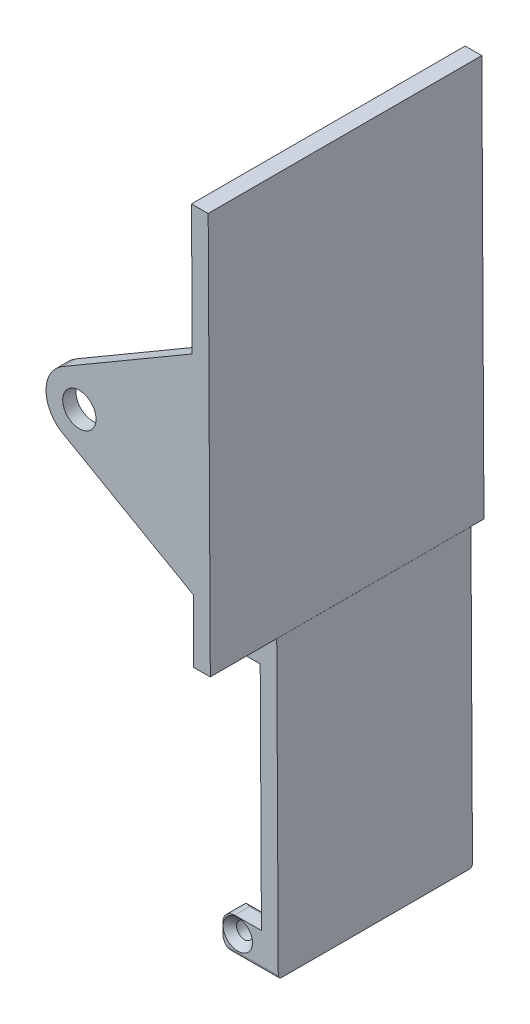
SolidWorks part; units mm, degrees
ref_plane "Front Plane" through (0, 0, 0) normal (0, 0, 1) x (1, 0, 0)
ref_plane "Top Plane" through (0, 0, 0) normal (0, 1, 0) x (1, 0, 0)
ref_plane "Right Plane" through (0, 0, 0) normal (1, 0, 0) x (0, 0, -1)
sketch "Sketch1" plane through (-32.9162, -0.1748, -0.0082) normal (1, 0.0053, 0.0002) x (0.0002, 0, -1)
  line L1 (-31.9268, 49.3585) -> (-29.2268, 49.3585)
  line L2 (-31.9268, 49.3585) -> (-31.9268, 53.8585)
  line L3 (-31.9268, 53.8585) -> (-29.2268, 53.8585)
  line L4 (-29.2268, 49.3585) -> (-29.2268, 53.8585)
  line L5 (-31.9268, 14.8585) -> (-29.2268, 14.8585)
  line L6 (-31.9268, 14.8585) -> (-31.9268, 9.7432)
  line L7 (-31.9268, 9.7432) -> (-29.2268, 9.7432)
  line L8 (-29.2268, 14.8585) -> (-29.2268, 9.7432)
  line L9 (-55.6268, 14.8585) -> (-58.3268, 14.8585)
  line L10 (-55.6268, 14.8585) -> (-55.6268, 9.7432)
  line L11 (-55.6268, 9.7432) -> (-58.3268, 9.7432)
  line L12 (-58.3268, 14.8585) -> (-58.3268, 9.7432)
  line L13 (-55.6268, 49.3585) -> (-58.3268, 49.3585)
  line L14 (-55.6268, 49.3585) -> (-55.6268, 53.8585)
  line L15 (-55.6268, 53.8585) -> (-58.3268, 53.8585)
  line L16 (-58.3268, 49.3585) -> (-58.3268, 53.8585)
  line L18 (-31.9268, 12.8585) -> (-31.9268, 9.0585) construction
  line L19 (-31.9268, 14.8585) -> (-29.2268, 14.8585) construction
  line L20 (-58.3268, 12.8585) -> (-58.3268, 9.0585) construction
  line L21 (-55.6268, 12.8585) -> (-55.6268, 9.0585) construction
  line L22 (-29.2268, 12.8585) -> (-29.2268, 9.0585) construction
  line L23 (-31.9268, 53.8585) -> (-29.2268, 53.8585) construction
  line L24 (-29.2268, 49.3585) -> (-31.9268, 49.3585) construction
  line L25 (-55.6268, 49.3585) -> (-58.3268, 49.3585) construction
  line L26 (-52.7264, 9.723) -> (-36.3268, 9.6085) construction
extrude "Boss-Extrude1" add sketch "Sketch1" along normal blind 5.8 from offset 0.25
sketch "Sketch2" plane through (-26.8663, -0.1427, -0.0067) normal (1, 0.0053, 0.0002) x (0.0002, 0, -1)
  line L1 (-29.2268, 9.7432) -> (-58.3268, 9.7432)
  line L2 (-29.2268, 9.7432) -> (-29.2268, 53.8585)
  line L3 (-29.2268, 53.8585) -> (-58.3268, 53.8585)
  line L4 (-58.3268, 9.7432) -> (-58.3268, 53.8585)
extrude "Boss-Extrude2" add sketch "Sketch2" along normal blind 2.5
hole_wizard "CSK for M2 Countersunk Flat Head Screw1" positions "Sketch4" profile "Sketch5" countersink size "M2" standard "ISO"
sketch "Sketch4" plane through (-0.0145, 0, 58.3268) normal (-0.0002, 0, 1) x (1, 0, 0.0002)
  arc A2 (-30.6956, 52.4462) -> (-30.685, 50.4462) centre (-30.6903, 51.4462) ccw construction
  arc A3 (-30.4885, 13.4467) -> (-30.4779, 11.4468) centre (-30.4832, 12.4468) ccw construction
  point P12 (-30.6903, 51.4462)
  point P14 (-30.4832, 12.4468)
sketch "Sketch5" plane through (-30.7049, 51.4462, 58.3192) normal (0.7071, 0.7071, 0.0002) x (0.7071, -0.7071, 0.0002)
  line L0 (0, 0) -> (0, 4.721)
  line L1 (0, 4.721) -> (1.2, 4)
  line L2 (1.2, 4) -> (1.2, 1)
  line L3 (1.2, 1) -> (2.2, 0)
  line L5 (2.2, 0) -> (0, 0)
  line L6 (-1.2, 1) -> (-2.2, 0) construction
  line L10 (0, 4.721) -> (-1.2, 4) construction
  line L11 (0, -6.35) -> (0, 107.95) construction
  dimension "Hole Dia." = 2.4
  dimension "Hole Depth" = 4
  dimension "Near C'Sink Dia." = 4.4
  dimension "Near C'Sink Angle" = 90
  dimension "Drill Angle" = 118
hole_wizard "CSK for M2 Countersunk Flat Head Screw2" positions "Sketch7" profile "Sketch6" countersink size "M2" standard "ISO"
sketch "Sketch7" plane through (-0.0073, 0, 29.2268) normal (0.0002, 0, -1) x (-1, 0, -0.0002)
  circle A1 centre (30.6903, 51.4462) radius 1.2 construction
  circle A2 centre (30.4832, 12.4468) radius 1.2 construction
  point P0 (30.6903, 51.4462)
  point P5 (30.4832, 12.4468)
sketch "Sketch6" plane through (-30.6976, 51.4462, 29.2192) normal (0.7071, 0.7071, 0.0002) x (-0.7071, 0.7071, -0.0002)
  line L0 (0, 0) -> (0, 4.721)
  line L1 (0, 4.721) -> (1.2, 4)
  line L2 (1.2, 4) -> (1.2, 1)
  line L3 (1.2, 1) -> (2.2, 0)
  line L5 (2.2, 0) -> (0, 0)
  line L6 (-1.2, 1) -> (-2.2, 0) construction
  line L10 (0, 4.721) -> (-1.2, 4) construction
  line L11 (0, -6.35) -> (0, 107.95) construction
  dimension "Hole Dia." = 2.4
  dimension "Hole Depth" = 4
  dimension "Near C'Sink Dia." = 4.4
  dimension "Near C'Sink Angle" = 90
  dimension "Drill Angle" = 118
fillet "Fillet2" radius 1.8 8 edges at (-32.7321, 9.5696, 56.9687) (-32.7593, 14.6847, 56.9687) (-32.7255, 9.5696, 30.5687) (-32.7527, 14.6848, 30.5687) (-32.936, 49.1843, 30.5687) (-32.9599, 53.6842, 30.5687) (-32.9664, 53.6842, 56.9687) (-32.9425, 49.1843, 56.9687)
fillet "Fillet3" radius 0.5 6 edges at (-28.959, 14.7049, 55.6196) (-28.9531, 14.7049, 31.9196) (-29.1364, 49.2045, 31.9196) (-29.1423, 49.2044, 55.6196) (-27.6825, 9.5964, 58.3199) (-27.6753, 9.5964, 29.2199) tangent propagation no
sketch "Sketch9" plane through (-24.3663, -0.1294, -0.0061) normal (1, 0.0053, 0.0002) x (0.0002, 0, -1)
  line L0 (-57.8268, 9.7433) -> (-29.7268, 9.7433) construction
  line L1 (-68.2768, 53.8661) -> (-27.2768, 53.8661)
  line L2 (-68.2768, 53.8661) -> (-68.2768, 113.8661)
  line L3 (-68.2768, 113.8661) -> (-27.2768, 113.8661)
  line L4 (-27.2768, 53.8661) -> (-27.2768, 113.8661)
  line L5 (-47.7768, 53.8661) -> (-47.7768, 9.7433) construction
  point P6 (-43.7768, 9.7433)
  dimension "D1" = 60
  dimension "D2" = 41
  dimension "D3" = 4
extrude "Boss-Extrude3" add sketch "Sketch9" against normal up to surface (2.5 mm away) separate body up to face at (-27.0473, 31.8884, 43.7701)
sketch "Sketch11" plane through (-0.017, -0.0001, 68.2768) normal (-0.0002, 0, 1) x (1, 0, 0.0002)
  line L6 (-27.3679, 94.303) -> (-46.8078, 82.9412)
  line L7 (-27.1524, 53.7226) -> (-27.4711, 113.7218) construction
  line L8 (-46.7618, 74.2811) -> (-27.2023, 63.1265)
  line L9 (-27.2023, 63.1265) -> (-27.3679, 94.303)
  line L10 (-24.6524, 53.7284) -> (-31.1523, 53.6938) construction
  arc A2 (-46.8078, 82.9412) -> (-46.7618, 74.2811) centre (-44.2849, 78.6244) ccw
  circle A3 centre (-44.2849, 78.6244) radius 2.5
  dimension "D2" = 5
  dimension "D3" = 25
  dimension "D1" = 5
  dimension "D4" = 17
  dimension "D5" = 60
extrude "Boss-Extrude4" add sketch "Sketch11" against normal blind 2
sketch "Sketch12" plane through (-26.8663, -0.1427, -0.0067) normal (-1, -0.0053, -0.0002) x (-0.0002, 0, 1)
  line L0 (47.7768, 53.8661) -> (47.7768, 117.036) construction
  line L1 (27.2768, 53.8661) -> (68.2768, 53.8661) construction
ref_plane "Plane1" through (-0.0119, -0.0001, 47.7768) normal (-0.0002, 0, 1) x (-0.0053, 1, 0)
mirror "Mirror1" about plane through (-0.0119, -0.0001, 47.7768) normal (-0.0002, 0, 1) of "Boss-Extrude4"
